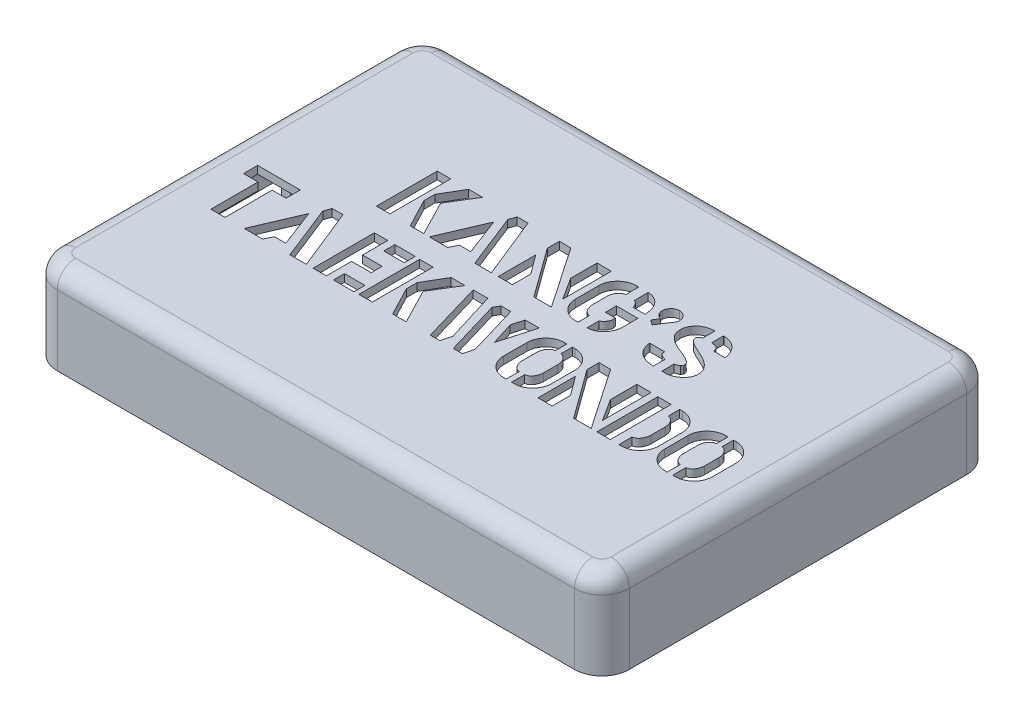
SolidWorks part; units mm, degrees
ref_plane "Front Plane" through (0, 0, 0) normal (0, 0, 1) x (1, 0, 0)
ref_plane "Top Plane" through (0, 0, 0) normal (0, 1, 0) x (1, 0, 0)
ref_plane "Right Plane" through (0, 0, 0) normal (1, 0, 0) x (0, 0, -1)
sketch "Sketch1" plane through (0, 0, 0) normal (0, 1, 0) x (1, 0, 0)
  line L0 (-41.5, -30.6) -> (-41.5, 24.85)
  line L1 (-37, -33.6) -> (48, -33.6)
  line L2 (-40, -30.6) -> (-40, 24.85)
  line L3 (-37, 27.85) -> (48, 27.85)
  line L4 (51, -30.6) -> (51, 24.85)
  line L5 (-40, -33.6) -> (51, 27.85) construction
  line L6 (-40, 27.85) -> (51, -33.6) construction
  line L7 (-37, 29.35) -> (48, 29.35)
  line L8 (52.5, -30.6) -> (52.5, 24.85)
  line L9 (-37, -35.1) -> (48, -35.1)
  line L10 (52.5, 24.85) -> (52.5, -30.6) construction
  line L11 (-41.5, -30.6) -> (-41.5, -26) construction
  line L16 (-37, 29.35) -> (48, 29.35) construction
  line L17 (48, -35.1) -> (-37, -35.1) construction
  arc A0 (48, -33.6) -> (51, -30.6) centre (48, -30.6) ccw
  arc A1 (-37, -33.6) -> (-40, -30.6) centre (-37, -30.6) cw
  arc A2 (-40, 24.85) -> (-37, 27.85) centre (-37, 24.85) cw
  arc A3 (48, 27.85) -> (51, 24.85) centre (48, 24.85) cw
  arc A4 (-41.5, 24.85) -> (-37, 29.35) centre (-37, 24.85) cw
  arc A5 (48, 29.35) -> (52.5, 24.85) centre (48, 24.85) cw
  arc A6 (48, -35.1) -> (52.5, -30.6) centre (48, -30.6) ccw
  arc A7 (-37, -35.1) -> (-41.5, -30.6) centre (-37, -30.6) cw
  dimension "D1" = 3
  dimension "D2" = 1.5
extrude "Boss-Extrude1" add sketch "Sketch1" along normal blind 1.25 contours A7 L9 A6 L8 A5 L7 A4 L0 L3 A3 L4 A0 L1 A1 L2 A2 | A3 L3 A2 L2 A1 L1 A0 L4 region at (-40.3603, 0, 2.875) region at (5.5, 0, 2.875)
extrude "Boss-Extrude2" add sketch "Sketch1<3>" against normal up to surface (13.28 mm away)
sketch "Sketch1<3>" plane through (0, 0, 0) normal (0, 1, 0) x (1, 0, 0) same geometry as "Sketch1"
sketch "Sketch2" plane through (0, 0, -29.35) normal (0, 0, -1) x (-1, 0, 0)
  line L5 (13.1593, -13.28) -> (-41.2921, -13.28)
  line L6 (13.1593, -13.28) -> (13.1593, -0.25)
  line L7 (13.1593, -0.25) -> (-41.2921, -0.25)
  line L30 (-41.2921, -13.28) -> (-41.2921, -0.25)
  line L33 (-40.7921, -13.28) -> (-40.7921, -0.75) construction
  line L37 (37, -13.28) -> (-48, -13.28) construction
  line L40 (-27.5421, -0.75) -> (-40.7921, -0.75) construction
  line L41 (12.6593, -13.28) -> (12.6593, -0.75) construction
  point P1 (-34.5685, -26.3233)
  point P5 (0, 0)
  dimension "D2" = 0.5
  dimension "D3" = 0.5
  dimension "D1" = 0.5
extrude "Cut-Extrude1" cut sketch "Sketch2" against normal up to next
fillet "Fillet1" radius 3 16 edges at (-40.182, 1.25, -28.032) (-41.5, 1.25, 2.875) (-40.182, 1.25, 33.782) (5.5, 1.25, 35.1) (51.182, 1.25, 33.782) (52.5, 1.25, 2.875) (51.182, 1.25, -28.032) (5.5, 1.25, -29.35) (-39.1213, 0, 32.7213) (-40, 0, 2.875) (-39.1213, 0, -26.9713) (5.5, 0, -27.85) (50.1213, 0, -26.9713) (51, 0, 2.875) (50.1213, 0, 32.7213) (5.5, 0, 33.6)
sketch "Sketch5" plane through (0, 1.25, 0) normal (0, 1, 0) x (1, 0, 0)
  line L0 (-38.5, 0) -> (49.5, 0) construction
  line L1 (-38.5, -14) -> (49.5, -14) construction
  line L2 (-38.5, 24.85) -> (-38.5, -30.6) construction
  line L3 (49.5, -30.6) -> (49.5, 24.85) construction
  text T0 "KANG'S" font "Stencil Gothic" height 10
  text T1 "TAEKWONDO" font "Stencil Gothic" height 10
  dimension "D1" = 14
extrude "Cut-Extrude3" cut sketch "Sketch5" against normal through all
sketch "Sketch6" plane through (-41.5, 0, 0) normal (-1, 0, 0) x (0, 0, 1)
  line L0 (-24.85, -13.28) -> (30.6, -13.28) construction
  line L1 (-26.45, -8.78) -> (-9.45, -8.78)
  line L2 (-26.45, -8.78) -> (-26.45, -13.28)
  line L3 (-26.45, -13.28) -> (-9.45, -13.28)
  line L4 (-9.45, -8.78) -> (-9.45, -13.28)
  line L5 (-26.45, -13.28) -> (-26.45, -23.58) construction
  line L6 (-6.25, -13.28) -> (7.95, -13.28)
  line L7 (-6.25, -13.28) -> (-6.25, -7.28)
  line L8 (-6.25, -7.28) -> (7.95, -7.28)
  line L9 (7.95, -13.28) -> (7.95, -7.28)
  line L10 (11.8, -13.28) -> (26, -13.28)
  line L11 (11.8, -13.28) -> (11.8, -7.28)
  line L12 (11.8, -7.28) -> (26, -7.28)
  line L13 (26, -13.28) -> (26, -7.28)
  line L14 (-25.95, -9.28) -> (-9.95, -9.28) construction
  line L15 (-5.75, -7.78) -> (7.45, -7.78) construction
  line L16 (12.3, -7.78) -> (25.5, -7.78) construction
  point P16 (0, 0)
  point P18 (0, 0)
  point P20 (0, 0)
  point P22 (0, 0)
  point P24 (0, 0)
  dimension "D1" = 0.5
  dimension "D2" = 0.5
  dimension "D3" = 0.5
extrude "Cut-Extrude4" cut sketch "Sketch6" against normal up to next
